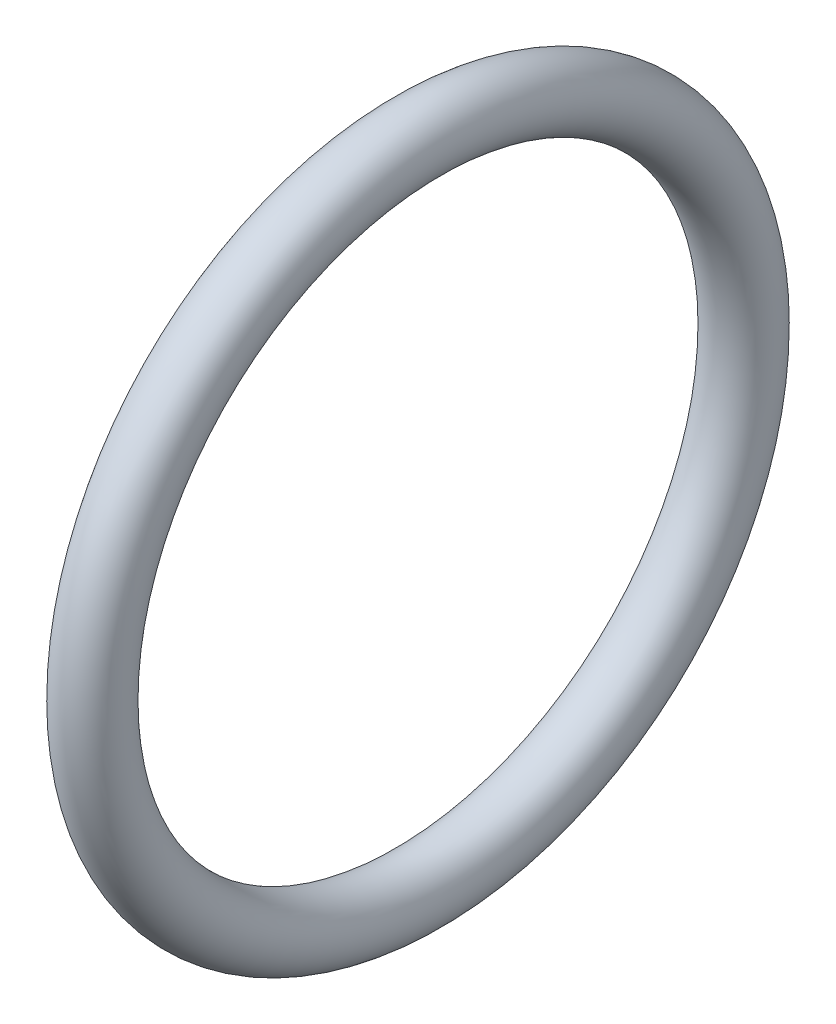
SolidWorks part; units mm, degrees
ref_plane "Plano frontal" through (0, 0, 0) normal (0, 0, 1) x (1, 0, 0)
ref_plane "Plano superior" through (0, 0, 0) normal (0, 1, 0) x (1, 0, 0)
ref_plane "Plano direito" through (0, 0, 0) normal (1, 0, 0) x (0, 0, -1)
sketch "Esboço1" plane through (0, 0, 0) normal (0, 0, 1) x (1, 0, 0)
  line L0 (0, 0) -> (0, 12.1) construction
  line L1 (0, 0) -> (21.9936, 0) construction
  circle A0 centre (0, 12.1) radius 1.2
  dimension "D1" = 2.4
  dimension "D2" = 12.1
revolve "Revolução1" add sketch "Esboço1" angle 360 about L1
ref_axis "Eixo1" through (-2.6271, 0, 0) along (1, 0, 0)
